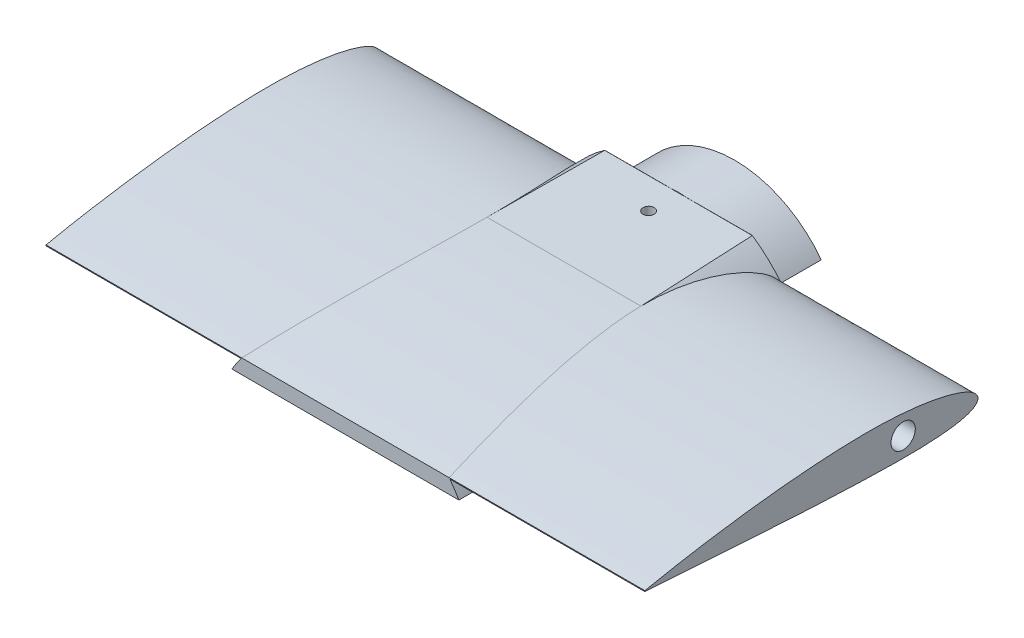
SolidWorks part; units mm, degrees
ref_plane "Front Plane" through (0, 0, 0) normal (0, 0, 1) x (1, 0, 0)
ref_plane "Top Plane" through (0, 0, 0) normal (0, 1, 0) x (1, 0, 0)
ref_plane "Right Plane" through (0, 0, 0) normal (1, 0, 0) x (0, 0, -1)
sketch "Sketch4" plane through (0, 0, 0) normal (0, 0, 1) x (1, 0, 0)
  line L0 (-30.3109, 17.5) -> (30.3109, 17.5)
  arc A1 (30.3109, 17.5) -> (-30.3109, 17.5) centre (0, 0) ccw
  dimension "D1" = 35
  dimension "D2" = 17.5
extrude "Exterior" add sketch "Sketch4" along normal blind 89 contours L0 A1
sketch "Sketch5" plane through (0, 0, 0) normal (0, 0, -1) x (-1, 0, 0)
  line L0 (30.3109, 17.5) -> (-30.3109, 17.5) construction
  line L1 (23.1247, 17.5) -> (-23.1247, 17.5)
  arc A0 (23.1247, 17.5) -> (-23.1247, 17.5) centre (0, 0) ccw
  dimension "D1" = 58
extrude "Boss-Extrude1" add sketch "Sketch5" along normal blind 15
curve "Curve3"
  spline degree 3 poles (0, 1.3, 1000) (0, 4.7133, 983.3426) (0, 11.531, 950.0715) (0, 24.0186, 883.4722) (0, 37.8548, 800.1781) (0, 52.175, 700.1592) (0, 64.1175, 600.1567) (0, 72.8619, 500.1109) (0, 78.7837, 400.0878) (0, 79.786, 316.6355) (0, 77.0249, 249.9395) (0, 72.979, 199.8766) (0, 66.5721, 149.7505) (0, 58.6825, 108.0331) (0, 49.7566, 74.7751) (0, 41.6416, 49.5609) (0, 32.1864, 28.1982) (0, 20.723, 9.771) (0, 0.8988, -6.2982) (0, -16.5264, 10.3934) (0, -24.4739, 28.476) (0, -30.5108, 49.7447) (0, -34.8393, 74.8759) (0, -38.5332, 108.2669) (0, -41.3764, 149.947) (0, -42.5163, 199.9941) (0, -42.3574, 250.0055) (0, -40.8857, 316.6783) (0, -38.2375, 400.0272) (0, -33.6287, 500.0334) (0, -27.6385, 600.0106) (0, -21.4122, 700.0048) (0, -15.1098, 800.0161) (0, -9.3053, 883.3314) (0, -4.8282, 950.0042) (0, -2.4761, 983.334) (0, -1.3, 1000) knots 0 0 0 0 0.025012 0.049959 0.099673 0.149206 0.198581 0.247805 0.296917 0.345953 0.370492 0.395091 0.419815 0.444799 0.45749 0.470406 0.483879 0.491264 0.503459 0.513609 0.520451 0.533235 0.545691 0.558032 0.582609 0.607135 0.631652 0.656174 0.705234 0.75432 0.803437 0.852566 0.901701 0.950849 0.975423 1 1 1 1
sketch "Sketch7" plane through (0, 0, 0) normal (1, 0, 0) x (0, 0, -1)
  line L0 (-89, 21.3887) -> (-89, 21.1573)
  line L1 (-89, 21.273) -> (0, 21.3903) construction
  line L2 (0, 21.3903) -> (-0.0573, 64.8516) construction
  line L7 (-89, 17.5) -> (0, 17.5) construction
  line L9 (0, 17.5) -> (0, 29) construction
  spline S1 degree 3 poles (-89, 21.3887) (-87.5176, 21.6924) (-84.5567, 22.2992) (-78.6297, 23.4105) (-71.2171, 24.6418) (-62.316, 25.9162) (-53.4164, 26.979) (-44.5129, 27.7573) (-35.6114, 28.2842) (-28.1847, 28.3735) (-22.2492, 28.1277) (-17.7939, 27.7677) (-13.3329, 27.1975) (-9.6203, 26.4954) (-6.6606, 25.701) (-4.4167, 24.9788) (-2.5155, 24.1374) (-0.8756, 23.1172) (0.5545, 21.353) (-0.931, 19.8022) (-2.5402, 19.095) (-4.433, 18.5577) (-6.6696, 18.1725) (-9.6412, 17.8438) (-13.3504, 17.5907) (-17.8043, 17.4893) (-22.255, 17.5034) (-28.1885, 17.6344) (-35.606, 17.8701) (-44.506, 18.2802) (-53.4034, 18.8133) (-62.3022, 19.3674) (-71.2026, 19.9283) (-78.6172, 20.4449) (-84.5507, 20.8433) (-87.5168, 21.0526) (-89, 21.1573) knots 0 0 0 0 0.025012 0.049959 0.099673 0.149206 0.198581 0.247805 0.296917 0.345953 0.370492 0.395091 0.419815 0.444799 0.45749 0.470406 0.483879 0.491264 0.503459 0.513609 0.520451 0.533235 0.545691 0.558032 0.582609 0.607135 0.631652 0.656174 0.705234 0.75432 0.803437 0.852566 0.901701 0.950849 0.975423 1 1 1 1
  dimension "D1" = 89
ref_plane "Plane1" through (80, 0, 0) normal (1, 0, 0) x (0, 0, -1)
ref_plane "Plane2" through (-80, 0, 0) normal (1, 0, 0) x (0, 0, -1)
sketch "Sketch8" plane through (80, 0, 0) normal (1, 0, 0) x (0, 0, -1)
  line L0 (-89, 21.3887) -> (-89, 21.1573)
  spline S0 degree 3 poles (-469.3669, 946.2185) (-209.3584, -26.81) (-147.9272, 10.417) (-78.6297, 23.4105) (-71.2171, 24.6418) (-62.316, 25.9162) (-53.4164, 26.979) (-44.5129, 27.7573) (-35.6114, 28.2842) (-28.1847, 28.3735) (-22.2492, 28.1277) (-17.7939, 27.7677) (-13.3329, 27.1975) (-9.6203, 26.4954) (-6.6606, 25.701) (-4.4167, 24.9788) (-2.5155, 24.1374) (-0.8756, 23.1172) (0.5545, 21.353) (-0.931, 19.8022) (-2.5402, 19.095) (-4.433, 18.5577) (-6.6696, 18.1725) (-9.6412, 17.8438) (-13.3504, 17.5907) (-17.8043, 17.4893) (-22.255, 17.5034) (-28.1885, 17.6344) (-35.606, 17.8701) (-44.506, 18.2802) (-53.4034, 18.8133) (-62.3022, 19.3674) (-71.2026, 19.9283) (-78.6172, 20.4449) (-191.4759, 28.0234) (-300.415, 49.2551) (-474.7288, -901.4445) knots -1.065698 -1.065698 -1.065698 -1.065698 0.025012 0.049959 0.099673 0.149206 0.198581 0.247805 0.296917 0.345953 0.370492 0.395091 0.419815 0.444799 0.45749 0.470406 0.483879 0.491264 0.503459 0.513609 0.520451 0.533235 0.545691 0.558032 0.582609 0.607135 0.631652 0.656174 0.705234 0.75432 0.803437 0.852566 0.901701 0.950849 0.975423 2.771414 2.771414 2.771414 2.771414 only from (-89, 21.3887) to (-89, 21.1573) construction
  spline S1 degree 3 poles (-89, 21.3887) (-87.5176, 21.6924) (-84.5567, 22.2992) (-78.6297, 23.4105) (-71.2171, 24.6418) (-62.316, 25.9162) (-53.4164, 26.979) (-44.5129, 27.7573) (-35.6114, 28.2842) (-28.1847, 28.3735) (-22.2492, 28.1277) (-17.7939, 27.7677) (-13.3329, 27.1975) (-9.6203, 26.4954) (-6.6606, 25.701) (-4.4167, 24.9788) (-2.5155, 24.1374) (-0.8756, 23.1172) (0.5545, 21.353) (-0.931, 19.8022) (-2.5402, 19.095) (-4.433, 18.5577) (-6.6696, 18.1725) (-9.6412, 17.8438) (-13.3504, 17.5907) (-17.8043, 17.4893) (-22.255, 17.5034) (-28.1885, 17.6344) (-35.606, 17.8701) (-44.506, 18.2802) (-53.4034, 18.8133) (-62.3022, 19.3674) (-71.2026, 19.9283) (-78.6172, 20.4449) (-84.5507, 20.8433) (-87.5168, 21.0526) (-89, 21.1573) knots 0 0 0 0 0.025012 0.049959 0.099673 0.149206 0.198581 0.247805 0.296917 0.345953 0.370492 0.395091 0.419815 0.444799 0.45749 0.470406 0.483879 0.491264 0.503459 0.513609 0.520451 0.533235 0.545691 0.558032 0.582609 0.607135 0.631652 0.656174 0.705234 0.75432 0.803437 0.852566 0.901701 0.950849 0.975423 1 1 1 1
sketch "Sketch9" plane through (-80, 0, 0) normal (1, 0, 0) x (0, 0, -1)
  line L0 (-89, 21.3887) -> (-89, 21.1573)
  spline S0 degree 3 poles (-469.3669, 946.2185) (-209.3584, -26.81) (-147.9272, 10.417) (-78.6297, 23.4105) (-71.2171, 24.6418) (-62.316, 25.9162) (-53.4164, 26.979) (-44.5129, 27.7573) (-35.6114, 28.2842) (-28.1847, 28.3735) (-22.2492, 28.1277) (-17.7939, 27.7677) (-13.3329, 27.1975) (-9.6203, 26.4954) (-6.6606, 25.701) (-4.4167, 24.9788) (-2.5155, 24.1374) (-0.8756, 23.1172) (0.5545, 21.353) (-0.931, 19.8022) (-2.5402, 19.095) (-4.433, 18.5577) (-6.6696, 18.1725) (-9.6412, 17.8438) (-13.3504, 17.5907) (-17.8043, 17.4893) (-22.255, 17.5034) (-28.1885, 17.6344) (-35.606, 17.8701) (-44.506, 18.2802) (-53.4034, 18.8133) (-62.3022, 19.3674) (-71.2026, 19.9283) (-78.6172, 20.4449) (-191.4759, 28.0234) (-300.415, 49.2551) (-474.7288, -901.4445) knots -1.065698 -1.065698 -1.065698 -1.065698 0.025012 0.049959 0.099673 0.149206 0.198581 0.247805 0.296917 0.345953 0.370492 0.395091 0.419815 0.444799 0.45749 0.470406 0.483879 0.491264 0.503459 0.513609 0.520451 0.533235 0.545691 0.558032 0.582609 0.607135 0.631652 0.656174 0.705234 0.75432 0.803437 0.852566 0.901701 0.950849 0.975423 2.771414 2.771414 2.771414 2.771414 only from (-89, 21.3887) to (-89, 21.1573) construction
  spline S1 degree 3 poles (-89, 21.3887) (-87.5176, 21.6924) (-84.5567, 22.2992) (-78.6297, 23.4105) (-71.2171, 24.6418) (-62.316, 25.9162) (-53.4164, 26.979) (-44.5129, 27.7573) (-35.6114, 28.2842) (-28.1847, 28.3735) (-22.2492, 28.1277) (-17.7939, 27.7677) (-13.3329, 27.1975) (-9.6203, 26.4954) (-6.6606, 25.701) (-4.4167, 24.9788) (-2.5155, 24.1374) (-0.8756, 23.1172) (0.5545, 21.353) (-0.931, 19.8022) (-2.5402, 19.095) (-4.433, 18.5577) (-6.6696, 18.1725) (-9.6412, 17.8438) (-13.3504, 17.5907) (-17.8043, 17.4893) (-22.255, 17.5034) (-28.1885, 17.6344) (-35.606, 17.8701) (-44.506, 18.2802) (-53.4034, 18.8133) (-62.3022, 19.3674) (-71.2026, 19.9283) (-78.6172, 20.4449) (-84.5507, 20.8433) (-87.5168, 21.0526) (-89, 21.1573) knots 0 0 0 0 0.025012 0.049959 0.099673 0.149206 0.198581 0.247805 0.296917 0.345953 0.370492 0.395091 0.419815 0.444799 0.45749 0.470406 0.483879 0.491264 0.503459 0.513609 0.520451 0.533235 0.545691 0.558032 0.582609 0.607135 0.631652 0.656174 0.705234 0.75432 0.803437 0.852566 0.901701 0.950849 0.975423 1 1 1 1
loft "Loft9" add profiles "Sketch8", "Sketch9" connector at (80, 21.3887, 89) connector at (-80, 21.3887, 89)
sketch "Sketch12" plane through (80, 0, 0) normal (1, 0, 0) x (0, 0, -1)
  line L0 (-89, 21.3887) -> (-89, 21.1573) construction
  line L1 (-89, 21.3887) -> (-89, 21.1573)
  line L2 (-89, 21.3887) -> (-97.2409, 26.9065)
  line L3 (-97.2409, 26.9065) -> (-90.2923, 42.7722)
  line L4 (-90.2923, 42.7722) -> (-30.1138, 44.0233)
  line L5 (-30.1138, 44.0233) -> (6.4186, 38.5184)
  line L6 (6.4186, 38.5184) -> (-0.0099, 28.9175)
  line L7 (0, 21.3903) -> (-0.0573, 64.8516) construction
  line L8 (-0.0099, 28.9175) -> (-30.6202, 28.3197)
  spline S0 degree 3 poles (-713.3875, 1915.884) (-239.966, -47.1163) (-164.6221, 7.2867) (-78.6297, 23.4105) (-71.2171, 24.6418) (-62.316, 25.9162) (-53.4164, 26.979) (-44.5129, 27.7573) (-35.6114, 28.2842) (-28.1847, 28.3735) (-22.2492, 28.1277) (-17.7939, 27.7677) (-13.3329, 27.1975) (-9.6203, 26.4954) (-6.6606, 25.701) (-4.4167, 24.9788) (-2.5155, 24.1374) (-0.8756, 23.1172) (0.5545, 21.353) (-0.931, 19.8022) (-2.5402, 19.095) (-4.433, 18.5577) (-6.6696, 18.1725) (-9.6412, 17.8438) (-13.3504, 17.5907) (-17.8043, 17.4893) (-22.255, 17.5034) (-28.1885, 17.6344) (-35.606, 17.8701) (-44.506, 18.2802) (-53.4034, 18.8133) (-62.3022, 19.3674) (-71.2026, 19.9283) (-78.6172, 20.4449) (-220.4152, 29.9667) (-357.7257, 61.3982) (-629.9057, -1889.2617) knots -1.346455 -1.346455 -1.346455 -1.346455 0.025012 0.049959 0.099673 0.149206 0.198581 0.247805 0.296917 0.345953 0.370492 0.395091 0.419815 0.444799 0.45749 0.470406 0.483879 0.491264 0.503459 0.513609 0.520451 0.533235 0.545691 0.558032 0.582609 0.607135 0.631652 0.656174 0.705234 0.75432 0.803437 0.852566 0.901701 0.950849 0.975423 3.250848 3.250848 3.250848 3.250848 only from (-89, 21.3887) to (-89, 21.1573) construction
  spline S1 degree 3 poles (-89, 21.3887) (-87.5176, 21.6924) (-84.5567, 22.2992) (-78.6297, 23.4105) (-71.2171, 24.6418) (-62.316, 25.9162) (-53.4164, 26.979) (-44.5129, 27.7573) (-36.9147, 28.2071) (-32.2817, 28.3107) (-30.6202, 28.3197) knots 0 0 0 0 0.025012 0.049959 0.099673 0.149206 0.198581 0.247805 0.296917 0.324377 0.324377 0.324377 0.324377
  spline S2 degree 3 poles (-89, 21.3887) (-87.5176, 21.6924) (-84.5567, 22.2992) (-78.6297, 23.4105) (-71.2171, 24.6418) (-62.316, 25.9162) (-53.4164, 26.979) (-44.5129, 27.7573) (-36.9147, 28.2071) (-32.2817, 28.3107) (-30.6202, 28.3197) knots 0 0 0 0 0.025012 0.049959 0.099673 0.149206 0.198581 0.247805 0.296917 0.324377 0.324377 0.324377 0.324377
extrude "Cut-Extrude1" cut sketch "Sketch12" against normal through all
sketch "Sketch13" plane through (-80, 0, 0) normal (-1, 0, 0) x (0, 0, 1)
  line L0 (20, 17.5005) -> (20, 27.9379) construction
  circle A0 centre (20, 22.7192) radius 3.25
  spline S0 degree 3 poles (89, 21.3887) (87.5176, 21.6924) (84.5567, 22.2992) (78.6297, 23.4105) (71.2171, 24.6418) (62.316, 25.9162) (53.4164, 26.979) (44.5129, 27.7573) (35.6114, 28.2842) (28.1847, 28.3735) (22.2492, 28.1277) (17.7939, 27.7677) (13.3329, 27.1975) (9.6203, 26.4954) (6.6606, 25.701) (4.4167, 24.9788) (2.5155, 24.1374) (0.8756, 23.1172) (-0.5545, 21.353) (0.931, 19.8022) (2.5402, 19.095) (4.433, 18.5577) (6.6696, 18.1725) (9.6412, 17.8438) (13.3504, 17.5907) (17.8043, 17.4893) (22.255, 17.5034) (28.1885, 17.6344) (35.606, 17.8701) (44.506, 18.2802) (53.4034, 18.8133) (62.3022, 19.3674) (71.2026, 19.9283) (78.6172, 20.4449) (84.5507, 20.8433) (87.5168, 21.0526) (89, 21.1573) knots 0 0 0 0 0.025012 0.049959 0.099673 0.149206 0.198581 0.247805 0.296917 0.345953 0.370492 0.395091 0.419815 0.444799 0.45749 0.470406 0.483879 0.491264 0.503459 0.513609 0.520451 0.533235 0.545691 0.558032 0.582609 0.607135 0.631652 0.656174 0.705234 0.75432 0.803437 0.852566 0.901701 0.950849 0.975423 1 1 1 1 construction
  point P8 (20, 22.7192)
  dimension "D1" = 6.5
  dimension "D2" = 20
extrude "Cut-Extrude2" cut sketch "Sketch13" against normal up to surface (160 mm away) up to face at (80, 23.6219, 69.5401)
ref_plane "Plane3" through (0, 30, 0) normal (0, 1, 0) x (1, 0, 0)
ref_plane "Plane4" through (0, 30, 0) normal (0, 1, 0) x (1, 0, 0)
sketch "Sketch15" plane through (0, 30, 0) normal (0, 1, 0) x (1, 0, 0)
  line L0 (0, -89) -> (0, 0) construction
  line L1 (-19.7174, -0.0099) -> (19.7174, -0.0099) construction
  circle A0 centre (0, -8.0099) radius 1.5
  dimension "D1" = 3
  dimension "D2" = 8
extrude "Cut-Extrude3" cut sketch "Sketch15" against normal through all
equation "\"fuse_diam\"= 0.07"
equation "\"fuse_rad\"= 0.035"
equation "\"battery_length\"= 0.076"
equation "\"battery_width\"= 0.034"
equation "\"battery_height\"= 0.051"
equation "\"bat_bay_length\"= 0.096"
equation "\"shell\"= 0.002"
equation "\"D1@Exterior\"=\"chord_length\""
equation "\"wing_shelf\"= 0.0175"
equation "\"chord_length\"= 0.089"
equation "\"tail_length\"= 0.26532000000000006"
equation "\"tail_diam\"= 0.035"
equation "\"connector\"= 0.06633000000000001"
equation "\"D2@Sketch4\"=\"wing_shelf\""
equation "\"D1@Sketch4\"=\"fuse_rad\""
equation "\"D1@Sketch5\"=\"fuse_diam\"-0.012"
equation "\"D1@Sketch7\"=\"chord_length\""
